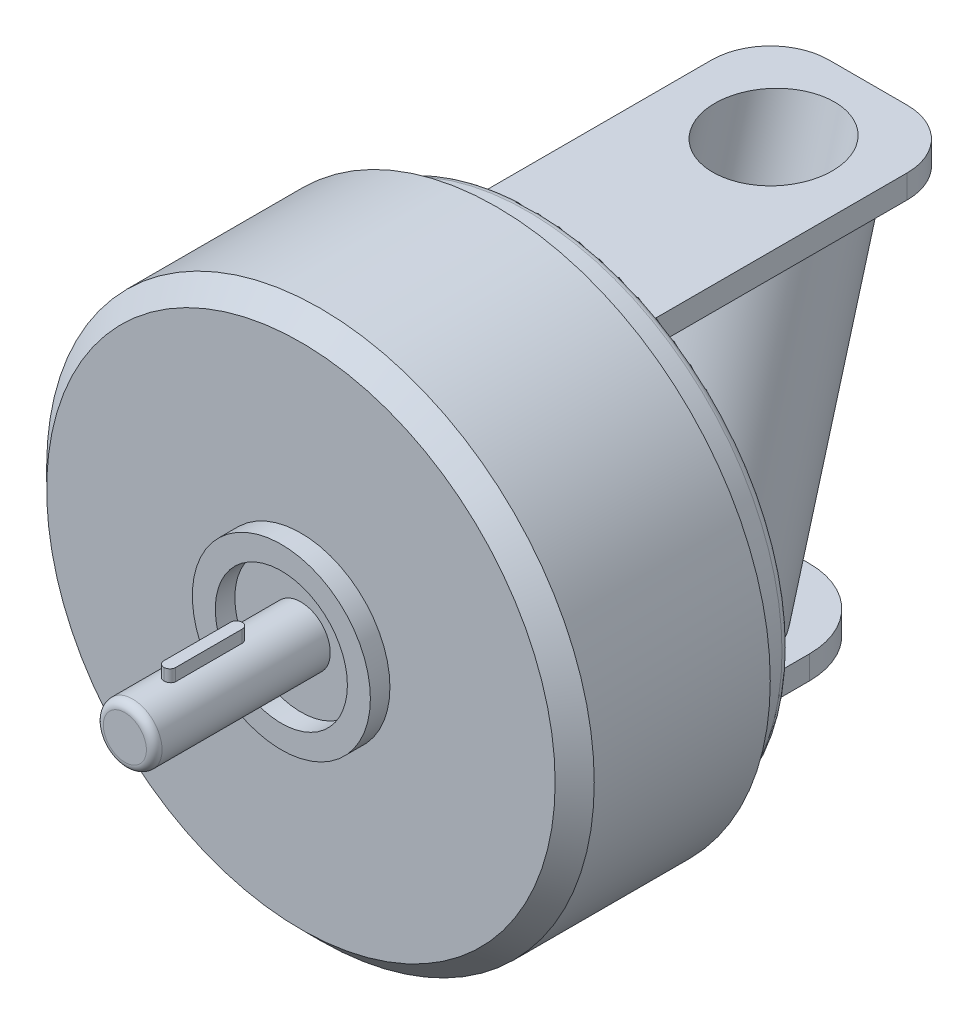
SolidWorks part; units mm, degrees
ref_plane "前视基准面" through (0, 0, 0) normal (0, 0, 1) x (1, 0, 0)
ref_plane "上视基准面" through (0, 0, 0) normal (0, 1, 0) x (1, 0, 0)
ref_plane "右视基准面" through (0, 0, 0) normal (1, 0, 0) x (0, 0, -1)
sketch "草图1" plane through (0, 0, 0) normal (0, 0, 1) x (1, 0, 0)
  circle A0 centre (0, 0) radius 65
  dimension "D1" = 130
extrude "凸台-拉伸1" add sketch "草图1" along normal blind 10
sketch "草图2" plane through (0, 0, 10) normal (0, 0, 1) x (1, 0, 0)
  circle A0 centre (0, 0) radius 70
  dimension "D1" = 140
extrude "凸台-拉伸2" add sketch "草图2" along normal blind 50
sketch "草图3" plane through (0, 0, 60) normal (0, 0, 1) x (1, 0, 0)
  circle A0 centre (0, 0) radius 22.76
  circle A1 centre (0, 0) radius 16.885
extrude "凸台-拉伸3" add sketch "草图3" along normal blind 5
sketch "草图4" plane through (0, 0, 60) normal (0, 0, 1) x (1, 0, 0)
  circle A0 centre (0, 0) radius 7.5
  dimension "D1" = 15
extrude "凸台-拉伸4" add sketch "草图4" along normal blind 45
sketch "草图5" plane through (0, 0, 0) normal (0, 0, -1) x (-1, 0, 0)
  line L1 (-25, -50) -> (25, -50)
  line L2 (-25, -50) -> (-25, 50)
  line L3 (-25, 50) -> (25, 50)
  line L4 (25, -50) -> (25, 50)
  line L5 (-25, -50) -> (25, 50) construction
  line L6 (-25, 50) -> (25, -50) construction
  point P0 (0, 0)
  dimension "D1" = 50
  dimension "D2" = 100
extrude "凸台-拉伸5" add sketch "草图5" along normal blind 85
sketch "草图6" plane through (0, 0, 0) normal (1, 0, 0) x (0, 0, -1)
  line L0 (23.911, -83.1803) -> (66.0701, 68.8404)
  line L1 (85, -50) -> (0, -50) construction
  line L2 (23.911, -83.1803) -> (7.5562, -142.1537) construction
  dimension "D1" = 74.5
sweep "切除-扫描1" cut path "草图6" circular profile diameter 30 parameters "D3"=30
shell "抽壳1" thickness 6 removed face at (-25, 0, -42.5) removed face at (25, 0, -42.5) removed face at (0, 0, -85)
fillet "圆角1" radius 15 2 edges at (-25, 47, -85) (25, 47, -85)
sketch "草图14" plane through (0, -44, 0) normal (0, 1, 0) x (1, 0, 0)
  line L0 (25, 70) -> (25, 0) construction
  line L1 (-25, 85) -> (25, 85)
  line L2 (-25, 85) -> (-25, 65)
  line L3 (-25, 65) -> (25, 65)
  line L4 (25, 85) -> (25, 65)
  dimension "D1" = 20
extrude "切除-拉伸1" cut sketch "草图14" against normal blind 70
fillet "圆角2" radius 20 2 edges at (-25, -47, -65) (25, -47, -65)
sketch "草图15" plane through (0, 0, 0) normal (0, 0, -1) x (-1, 0, 0)
  line L0 (-25, 50) -> (-25, 44) construction
  line L1 (-25, 49.9166) -> (25, 49.9166)
  line L2 (-25, 49.9166) -> (-25, -50)
  line L3 (-25, -50) -> (25, -50)
  line L4 (25, 49.9166) -> (25, -50)
extrude "凸台-拉伸6" add sketch "草图15" against normal blind 10
fillet "圆角3" radius 2 9 edges at (0, -44, 0) (25, -47, 0) (0, -50, 0) (-25, -47, 0) (65, 0, 0) (0, 50, 0) (25, 47, 0) (0, 44, 0) (-25, 47, 0)
chamfer "倒角1" distance 5 angle 45 1 edges at (70, 0, 60)
fillet "圆角4" radius 2 1 edges at (7.5, 0, 105)
ref_plane "基准面1" through (0, 0, 95) normal (0, 0, 1) x (1, 0, 0)
sketch "草图27" plane through (0, 0, 95) normal (0, 0, 1) x (1, 0, 0)
  line L1 (-1.5, 4.5) -> (1.5, 4.5)
  line L2 (-1.5, 4.5) -> (-1.5, 10.5)
  line L3 (-1.5, 10.5) -> (1.5, 10.5)
  line L4 (1.5, 4.5) -> (1.5, 10.5)
  line L5 (-1.5, 4.5) -> (1.5, 10.5) construction
  line L6 (-1.5, 10.5) -> (1.5, 4.5) construction
  circle A0 centre (0, 0) radius 7.5 construction
  point P0 (0, 7.5)
  dimension "D1" = 3
  dimension "D2" = 6
extrude "凸台-拉伸7" add sketch "草图27" against normal blind 20
fillet "圆角5" radius 1.5 4 edges at (1.5, 8.9242, 75) (-1.5, 8.9242, 75) (1.5, 8.9242, 95) (-1.5, 8.9242, 95)
